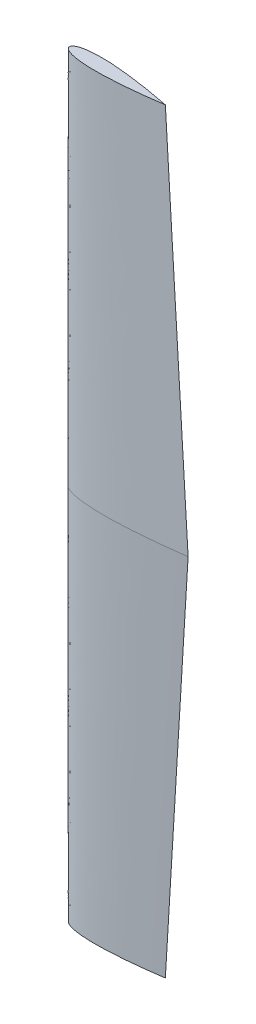
SolidWorks part; units mm, degrees
ref_plane "Front Plane" through (0, 0, 0) normal (0, 0, 1) x (1, 0, 0)
ref_plane "Top Plane" through (0, 0, 0) normal (0, 1, 0) x (1, 0, 0)
ref_plane "Right Plane" through (0, 0, 0) normal (1, 0, 0) x (0, 0, -1)
sketch "rootSketch" plane through (0, 0, 0) normal (0, 1, 0) x (1, 0, 0)
  line L0 (0, 0) -> (1500, 0) construction
  line L2 (128.5597, -43.5132) -> (131.2819, 34.4393) construction
  line L3 (0, 0) -> (519.6832, -18.1477) construction
  spline S0 degree 4 poles (0, 0) (-0.0002, 0.5667) (0.0539, 1.4837) (0.2619, 2.8011) (0.7802, 4.5001) (1.4742, 6.0739) (2.4882, 7.7775) (3.9235, 9.6383) (5.9814, 11.7335) (9.009, 14.164) (13.6174, 17.0522) (20.6576, 20.4152) (31.5744, 24.2573) (47.947, 28.2443) (72.4332, 31.9567) (104.0698, 34.1521) (136.0098, 34.3381) (166.235, 33.2839) (196.4193, 31.454) (226.5574, 28.9572) (256.6325, 25.7941) (286.6468, 22.1119) (311.6202, 18.7476) (329.0817, 16.251) (344.0355, 14.0177) (356.4869, 12.0973) (366.4445, 10.5258) (376.3928, 8.9212) (386.3424, 7.2818) (398.7604, 5.1939) (413.6712, 2.6185) (431.016, -0.4739) (450.8699, -4.1527) (468.1425, -7.4745) (483.0472, -10.4366) (495.2678, -12.9268) (504.1461, -14.7753) (511.0949, -16.2427) (518.4786, -17.8275) (522.2279, -18.6407) (527.6244, -19.8208) (532.0536, -20.8023) (537.2059, -21.9505) (542.7161, -23.1966) (549.3318, -24.7107) (555.7529, -26.2044) (561.4841, -27.5553) (565.9112, -28.6133) (569.17, -29.398) (570.7837, -29.7889) (571.5942, -29.9857) (571.9999, -30.0843) knots 0 0 0 0 0 0.003844 0.00624 0.009023 0.012042 0.015499 0.019677 0.02495 0.031949 0.041817 0.056547 0.07785 0.11044 0.156133 0.224611 0.293088 0.327327 0.361566 0.430043 0.498521 0.53276 0.566998 0.601237 0.618356 0.635476 0.652595 0.669715 0.686834 0.703953 0.738192 0.772431 0.80667 0.840908 0.858028 0.875147 0.892266 0.900826 0.909386 0.920713 0.926376 0.932039 0.943366 0.954693 0.96602 0.977346 0.988673 0.994337 0.997168 1 1 1 1 1 construction
  spline S1 degree 4 poles (0, 0) (-0.0002, 0.5667) (0.0539, 1.4837) (0.2619, 2.8011) (0.7802, 4.5001) (1.4742, 6.0739) (2.4882, 7.7775) (3.9235, 9.6383) (5.9814, 11.7335) (9.009, 14.164) (13.6174, 17.0522) (20.6576, 20.4152) (31.5744, 24.2573) (47.947, 28.2443) (72.4332, 31.9567) (104.0698, 34.1521) (136.0098, 34.3381) (166.235, 33.2839) (196.4193, 31.454) (226.5574, 28.9572) (256.6325, 25.7941) (286.6468, 22.1119) (311.6202, 18.7476) (329.0817, 16.251) (344.0355, 14.0177) (356.4869, 12.0973) (366.4445, 10.5258) (376.3928, 8.9212) (386.3424, 7.2818) (398.7604, 5.1939) (413.6712, 2.6185) (431.016, -0.4739) (450.8699, -4.1527) (468.1425, -7.4745) (483.0472, -10.4366) (495.2678, -12.9268) (504.1461, -14.7753) (511.0949, -16.2427) (516.6431, -17.4335) (518.8802, -17.9162) (520, -18.1588) knots 0 0 0 0 0 0.003844 0.00624 0.009023 0.012042 0.015499 0.019677 0.02495 0.031949 0.041817 0.056547 0.07785 0.11044 0.156133 0.224611 0.293088 0.327327 0.361566 0.430043 0.498521 0.53276 0.566998 0.601237 0.618356 0.635476 0.652595 0.669715 0.686834 0.703953 0.738192 0.772431 0.80667 0.840908 0.858028 0.875147 0.892266 0.900826 0.909386 0.909386 0.909386 0.909386 0.909386
  spline S2 degree 4 poles (0, 0) (-0.0398, -0.5653) (-0.0497, -1.4839) (0.0659, -2.8126) (0.4644, -4.5436) (1.0469, -6.162) (1.9396, -7.9321) (3.2416, -9.8885) (5.1484, -12.1221) (7.9991, -14.7579) (12.3947, -17.9606) (19.1832, -21.8064) (29.8054, -26.4007) (45.86, -31.5201) (70.0276, -36.9315) (101.4339, -41.3285) (133.2831, -43.742) (163.5083, -44.7988) (193.7467, -45.0789) (223.9856, -44.6905) (254.208, -43.633) (284.4061, -42.0535) (309.5534, -40.4395) (327.1464, -39.167) (342.2196, -37.9822) (354.7746, -36.9351) (364.8177, -36.0621) (374.8536, -35.1553) (384.8933, -34.214) (397.4267, -32.9974) (412.4809, -31.4683) (429.9991, -29.5934) (450.0613, -27.3086) (467.5235, -25.1997) (482.5986, -23.2845) (494.9631, -21.6528) (503.9487, -20.4281) (510.983, -19.4491) (518.4592, -18.3832) (522.2561, -17.8335) (527.7218, -17.0327) (532.2086, -16.3625) (537.4285, -15.5765) (543.0122, -14.7179) (549.7173, -13.6689) (556.227, -12.6268) (562.0386, -11.679) (566.5286, -10.9324) (569.8342, -10.3769) (571.4713, -10.0995) (572.2935, -9.9598) (572.7051, -9.8897) knots 0 0 0 0 0 0.003844 0.00624 0.009023 0.012042 0.015499 0.019677 0.02495 0.031949 0.041817 0.056547 0.07785 0.11044 0.156133 0.224611 0.293088 0.327327 0.361566 0.430043 0.498521 0.53276 0.566998 0.601237 0.618356 0.635476 0.652595 0.669715 0.686834 0.703953 0.738192 0.772431 0.80667 0.840908 0.858028 0.875147 0.892266 0.900826 0.909386 0.920713 0.926376 0.932039 0.943366 0.954693 0.96602 0.977346 0.988673 0.994337 0.997168 1 1 1 1 1 construction
  spline S3 degree 4 poles (0, 0) (-0.0398, -0.5653) (-0.0497, -1.4839) (0.0659, -2.8126) (0.4644, -4.5436) (1.0469, -6.162) (1.9396, -7.9321) (3.2416, -9.8885) (5.1484, -12.1221) (7.9991, -14.7579) (12.3947, -17.9606) (19.1832, -21.8064) (29.8054, -26.4007) (45.86, -31.5201) (70.0276, -36.9315) (101.4339, -41.3285) (133.2831, -43.742) (163.5083, -44.7988) (193.7467, -45.0789) (223.9856, -44.6905) (254.208, -43.633) (284.4061, -42.0535) (309.5534, -40.4395) (327.1464, -39.167) (342.2196, -37.9822) (354.7746, -36.9351) (364.8177, -36.0621) (374.8536, -35.1553) (384.8933, -34.214) (397.4267, -32.9974) (412.4809, -31.4683) (429.9991, -29.5934) (450.0613, -27.3086) (467.5235, -25.1997) (482.5986, -23.2845) (494.9631, -21.6528) (503.9487, -20.4281) (510.983, -19.4491) (516.6007, -18.6482) (518.866, -18.3227) (520, -18.1588) knots 0 0 0 0 0 0.003844 0.00624 0.009023 0.012042 0.015499 0.019677 0.02495 0.031949 0.041817 0.056547 0.07785 0.11044 0.156133 0.224611 0.293088 0.327327 0.361566 0.430043 0.498521 0.53276 0.566998 0.601237 0.618356 0.635476 0.652595 0.669715 0.686834 0.703953 0.738192 0.772431 0.80667 0.840908 0.858028 0.875147 0.892266 0.900826 0.909386 0.909386 0.909386 0.909386 0.909386
  point P10 (129.9208, -4.5369)
  dimension "incidenceAngle" = 2
  dimension "rootChord" = 520
  dimension "rootQuarterChord" = 130
  dimension "rootMaxThickness" = 78
ref_plane "Plane1" through (0, 1599.9984, 0) normal (0, 1, 0) x (1, 0, 0)
sketch "tipSketch" plane through (0, 1599.9984, 0) normal (0, 1, 0) x (1, 0, 0)
  line L0 (218.7894, 0) -> (520.1012, 0) construction
  line L3 (0, 0) -> (415.8686, -10.4541) construction
  line L4 (103.1831, -33.8037) -> (104.7512, 28.5766) construction
  spline S0 degree 4 poles (0, 0) (-0.0002, 0.4537) (0.0432, 1.1873) (0.2092, 2.2403) (0.622, 3.5997) (1.1738, 4.8591) (1.979, 6.224) (3.119, 7.7179) (4.7533, 9.4041) (7.1589, 11.3667) (10.8233, 13.7089) (16.4269, 16.4521) (25.1251, 19.6122) (38.1838, 22.9355) (57.7325, 26.1075) (83.0112, 28.1255) (112.5812, 28.6004) (140.7847, 27.6731) (164.9198, 26.1674) (185.0039, 24.5248) (201.0529, 23.0087) (217.0841, 21.3136) (233.0976, 19.4598) (249.0937, 17.463) (265.0735, 15.3362) (279.0406, 13.3702) (291.0035, 11.6142) (300.9637, 10.1058) (308.9311, 8.8715) (318.8781, 7.2968) (330.8189, 5.3519) (344.7148, 3.0109) (360.6136, 0.2213) (374.4576, -2.3054) (386.387, -4.559) (396.1959, -6.4619) (403.2749, -7.8662) (408.898, -8.9988) (414.744, -10.1962) (418.3515, -10.9434) (424.1991, -12.1675) (428.7951, -13.1496) (434.3702, -14.3507) (439.3394, -15.4433) (444.6879, -16.6318) (449.7679, -17.7825) (453.7438, -18.6936) (456.289, -19.2854) (457.6027, -19.5914) knots 0 0 0 0 0 0.003846 0.006245 0.009023 0.012045 0.015501 0.01968 0.024954 0.031954 0.041824 0.056556 0.077861 0.110456 0.156157 0.224645 0.293132 0.36162 0.395864 0.430108 0.464352 0.498596 0.53284 0.567084 0.601327 0.635571 0.652693 0.669815 0.686937 0.704059 0.738303 0.772547 0.806791 0.841035 0.858157 0.875279 0.892401 0.900962 0.909523 0.920832 0.932142 0.943452 0.954761 0.966071 0.977381 0.98869 1 1 1 1 1 construction
  spline S1 degree 4 poles (0, 0) (-0.0002, 0.4537) (0.0432, 1.1873) (0.2092, 2.2403) (0.622, 3.5997) (1.1738, 4.8591) (1.979, 6.224) (3.119, 7.7179) (4.7533, 9.4041) (7.1589, 11.3667) (10.8233, 13.7089) (16.4269, 16.4521) (25.1251, 19.6122) (38.1838, 22.9355) (57.7325, 26.1075) (83.0112, 28.1255) (112.5812, 28.6004) (140.7847, 27.6731) (164.9198, 26.1674) (185.0039, 24.5248) (201.0529, 23.0087) (217.0841, 21.3136) (233.0976, 19.4598) (249.0937, 17.463) (265.0735, 15.3362) (279.0406, 13.3702) (291.0035, 11.6142) (300.9637, 10.1058) (308.9311, 8.8715) (318.8781, 7.2968) (330.8189, 5.3519) (344.7148, 3.0109) (360.6136, 0.2213) (374.4576, -2.3054) (386.387, -4.559) (396.1959, -6.4619) (403.2749, -7.8662) (408.898, -8.9988) (413.2926, -9.8989) (415.1026, -10.2718) (416, -10.4574) knots 0 0 0 0 0 0.003846 0.006245 0.009023 0.012045 0.015501 0.01968 0.024954 0.031954 0.041824 0.056556 0.077861 0.110456 0.156157 0.224645 0.293132 0.36162 0.395864 0.430108 0.464352 0.498596 0.53284 0.567084 0.601327 0.635571 0.652693 0.669815 0.686937 0.704059 0.738303 0.772547 0.806791 0.841035 0.858157 0.875279 0.892401 0.900962 0.909523 0.909523 0.909523 0.909523 0.909523
  spline S2 degree 4 poles (0, 0) (-0.023, -0.4531) (-0.0166, -1.1879) (0.0964, -2.248) (0.4403, -3.6264) (0.9282, -4.9119) (1.6638, -6.3155) (2.7273, -7.8649) (4.2748, -9.6311) (6.5788, -11.712) (10.1209, -14.2354) (15.5795, -17.2566) (24.1079, -20.8498) (36.9832, -24.825) (56.3478, -28.9753) (81.4933, -32.2609) (111.002, -34.2208) (139.2165, -34.7118) (163.3968, -34.4206) (183.538, -33.7892) (199.6429, -33.0814) (215.739, -32.1939) (231.8255, -31.147) (247.9017, -29.9565) (263.9681, -28.6353) (278.0164, -27.3735) (290.0524, -26.2208) (300.0758, -25.2147) (308.0952, -24.3823) (318.1087, -23.3094) (330.1321, -21.967) (344.1281, -20.3271) (360.147, -18.3399) (374.1004, -16.5119) (386.128, -14.8605) (396.0201, -13.4529) (403.1608, -12.406) (408.8337, -11.5574) (414.7324, -10.6552) (418.373, -10.0902) (424.2747, -9.1615) (428.9142, -8.4115) (434.5426, -7.4921) (439.5604, -6.6505) (444.9619, -5.7323) (450.0933, -4.8382) (454.1099, -4.1281) (456.6816, -3.6649) (458.0091, -3.4253) knots 0 0 0 0 0 0.003846 0.006245 0.009023 0.012045 0.015501 0.01968 0.024954 0.031954 0.041824 0.056556 0.077861 0.110456 0.156157 0.224645 0.293132 0.36162 0.395864 0.430108 0.464352 0.498596 0.53284 0.567084 0.601327 0.635571 0.652693 0.669815 0.686937 0.704059 0.738303 0.772547 0.806791 0.841035 0.858157 0.875279 0.892401 0.900962 0.909523 0.920832 0.932142 0.943452 0.954761 0.966071 0.977381 0.98869 1 1 1 1 1 construction
  spline S3 degree 4 poles (0, 0) (-0.023, -0.4531) (-0.0166, -1.1879) (0.0964, -2.248) (0.4403, -3.6264) (0.9282, -4.9119) (1.6638, -6.3155) (2.7273, -7.8649) (4.2748, -9.6311) (6.5788, -11.712) (10.1209, -14.2354) (15.5795, -17.2566) (24.1079, -20.8498) (36.9832, -24.825) (56.3478, -28.9753) (81.4933, -32.2609) (111.002, -34.2208) (139.2165, -34.7118) (163.3968, -34.4206) (183.538, -33.7892) (199.6429, -33.0814) (215.739, -32.1939) (231.8255, -31.147) (247.9017, -29.9565) (263.9681, -28.6353) (278.0164, -27.3735) (290.0524, -26.2208) (300.0758, -25.2147) (308.0952, -24.3823) (318.1087, -23.3094) (330.1321, -21.967) (344.1281, -20.3271) (360.147, -18.3399) (374.1004, -16.5119) (386.128, -14.8605) (396.0201, -13.4529) (403.1608, -12.406) (408.8337, -11.5574) (413.2679, -10.8792) (415.0944, -10.5977) (416, -10.4574) knots 0 0 0 0 0 0.003846 0.006245 0.009023 0.012045 0.015501 0.01968 0.024954 0.031954 0.041824 0.056556 0.077861 0.110456 0.156157 0.224645 0.293132 0.36162 0.395864 0.430108 0.464352 0.498596 0.53284 0.567084 0.601327 0.635571 0.652693 0.669815 0.686937 0.704059 0.738303 0.772547 0.806791 0.841035 0.858157 0.875279 0.892401 0.900962 0.909523 0.909523 0.909523 0.909523 0.909523
  point P10 (103.9672, -2.6135)
  dimension "incidenceAngle" = 1.44
  dimension "tipChord" = 416
  dimension "tipQuarterChord" = 104
  dimension "tipMaxThickness" = 62.4
  dimension "sweepOffset" = 0
loft "Loft1" add profiles "rootSketch", "tipSketch" connector at (0, 0, 0) connector at (0, 1599.9984, 0)
mirror "Mirror1" about plane through (0, 0, 0) normal (0, 1, 0) of "Loft1"
ref_plane "Plane2" through (520, 0, 0) normal (1, 0, 0) x (0, 0, -1)
sketch "elevatorSketch" plane through (0, 0, 0) normal (0, 0, 1) x (1, 0, 0)
  line L0 (315.1976, 0.1247) -> (268.5272, 1196.7988)
  line L1 (0, 1199.9988) -> (265.2, 1199.9988) construction
  line L2 (0, 0) -> (312, 0) construction
  line L3 (-0.0313, 0) -> (520, 0) construction
  line L4 (312, 0) -> (265.2, 1199.9988)
  line L5 (268.5272, 1196.7988) -> (785.2, 1196.7988)
  line L7 (265.2, 1199.9988) -> (785.2, 1199.9988)
  line L8 (312, 0) -> (315.1976, 0.1247)
  line L9 (785.2, 1199.9988) -> (785.2, 1196.7988)
  dimension "elevatorEndyLoc" = 1199.9988
  dimension "elevatorEndxLoc" = 265.2
  dimension "D1" = 312
  dimension "D2" = 520
  dimension "D3" = 3.2
extrude "Cut-Extrude2" [suppressed] cut sketch "elevatorSketch" against normal blind 200 and the other way blind 200 contours L0 L5 L9 L7 L4 L8
mirror "Mirror2" [suppressed] about plane through (0, 0, 0) normal (0, 1, 0)
equation "\"rootChord\"= 0.52"
equation "\"NACAairfoil\"= 0015"
equation "\"incidentAngle\"= 2"
equation "\"aspectRatio\"= 6.8376"
equation "\"taperRatio\"= 0.8"
equation "\"sweepAngle\"= 0'H-stab sweep angle"
equation "\"rootChord@rootSketch\"=(\"rootChord\"+\"rootChord\")/2"
equation "\"rootQuarterChord@rootSketch\" = \"rootChord@rootSketch\" / 4"
equation "\"rootMaxThickness@rootSketch\" = \"rootChord\" * \"NACAairfoil\" / 100"
equation "\"halfSpan@Plane1\"=\"halfSpan\""
equation "\"tipQuarterChord@tipSketch\"=\"tipChord@tipSketch\"/4"
equation "\"tipMaxThickness@tipSketch\"=\"tipChord@tipSketch\"*\"NACAairfoil\"/100"
equation "\"rootChord@Plane2\"=\"rootChord@rootSketch\""
equation "\"elevatorWidth\"= 0.75'Elevator width as a percentage of H-stab span"
equation "\"elevatorEndyLoc@elevatorSketch\"=\"elevatorWidth\"*\"halfSpan@Plane1\""
equation "\"elevatorEndxLoc@elevatorSketch\"=\"elevatorEndyLoc@elevatorSketch\" * tan ( \"sweepAngle\" )  + 0.6 *  ( \"rootChord@rootSketch\" + \"elevatorEndyLoc@elevatorSketch\" *  (  (  ( \"tipChord@tipSketch\" - \"rootChord@rootSketch\" )  / \"halfSpan@Plane1\" )  )  )"
equation "\"D1@elevatorSketch\"=0.6*\"rootChord@rootSketch\""
equation "\"D2@elevatorSketch\"=1*\"rootChord@rootSketch\""
equation "\"D3@elevatorSketch\" = \"halfSpan\" / 500"
equation "\"halfSpan\"= \"rootChord\" * ( 1 + \"taperRatio\" ) / 2 * \"aspectRatio\" / 2'H-stab half Span"
equation "\"sweepOffset@tipSketch\" = \"halfSpan\" * tan ( \"sweepAngle\" ) "
equation "\"incidenceAngle@rootSketch\"=\"incidentAngle\""
